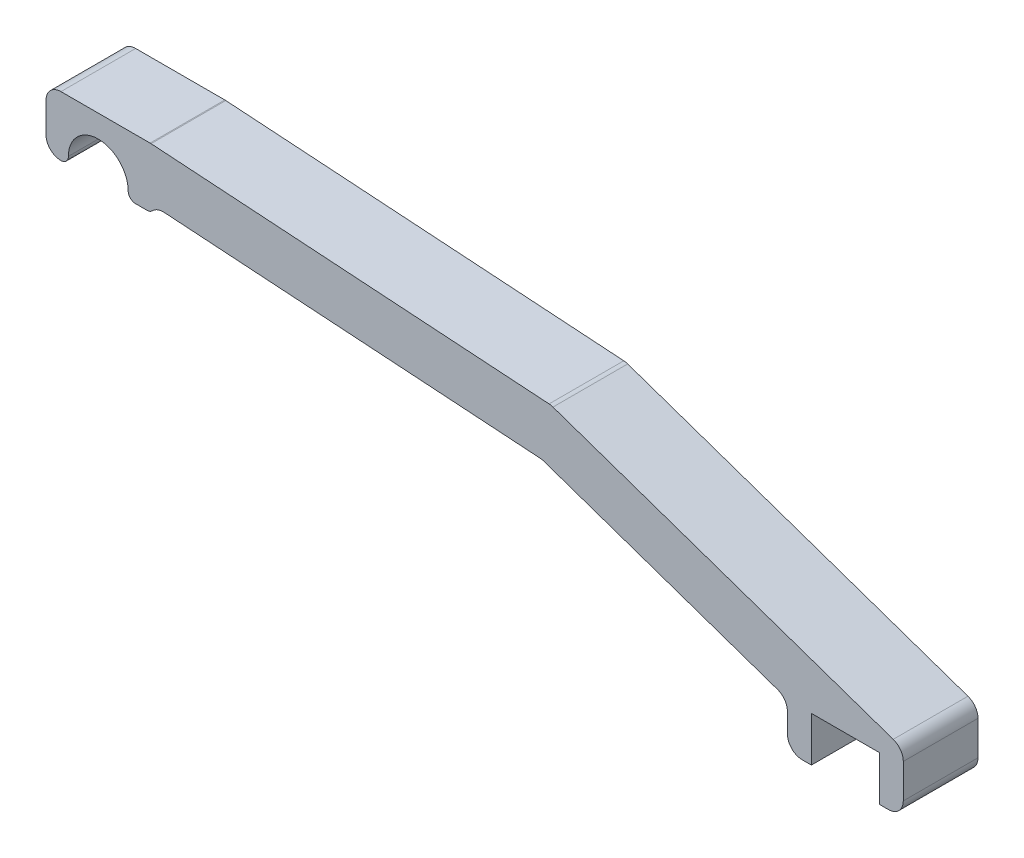
SolidWorks part; units mm, degrees
ref_plane "Спереди" through (0, 0, 0) normal (0, 0, 1) x (1, 0, 0)
ref_plane "Сверху" through (0, 0, 0) normal (0, 1, 0) x (1, 0, 0)
ref_plane "Справа" through (0, 0, 0) normal (1, 0, 0) x (0, 0, -1)
sketch "Эскиз1" plane through (0, 0, 0) normal (0, 0, 1) x (1, 0, 0)
  line L0 (95.45, -20.85) -> (95.45, -14.85)
  line L1 (92.2452, -12.85) -> (107.7548, -12.85)
  line L2 (92.2452, -12.85) -> (92.2452, -20.85)
  line L3 (92.2452, -20.85) -> (95.45, -20.85)
  line L4 (107.7548, -12.85) -> (107.7548, -20.85)
  line L5 (95.45, -14.85) -> (104.55, -14.85)
  line L6 (104.55, -14.85) -> (104.55, -20.85)
  line L7 (104.55, -20.85) -> (107.7548, -20.85)
  line L8 (0, 0) -> (60, 0) construction
  line L9 (60, 0) -> (100.8, -14.85) construction
  line L10 (60.6078, 3.4468) -> (59.3922, -3.4468)
  line L11 (-7, 7) -> (7, 7)
  line L12 (-7, 7) -> (-7, -1)
  line L14 (7, 7) -> (7, -1)
  line L15 (-7, -1) -> (-3.873, -1)
  line L16 (3.873, -1) -> (7, -1)
  line L17 (60.6078, 3.4468) -> (107.7548, -12.85)
  line L18 (59.3922, -3.4468) -> (92.2452, -14.8028)
  line L19 (60.6078, 3.4468) -> (7, 7)
  line L20 (59.3922, -3.4468) -> (7, 0.0258)
  arc A0 (3.873, -1) -> (-3.873, -1) centre (0, 0) ccw
  point P12 (100, -14.85)
  point P21 (60, 0)
  dimension "D1" = 8
  dimension "D2" = 9.1
  dimension "D3" = 6
  dimension "D4" = 2
  dimension "D5" = 14.85
  dimension "D6" = 60
  dimension "D7" = 100
  dimension "D8" = 7
  dimension "D9" = 160
  dimension "D10" = 80
  dimension "D11" = 7
  dimension "D12" = 7
  dimension "D13" = 7
  dimension "D14" = 1
extrude "Бобышка-Вытянуть1" add sketch "Эскиз1" along normal blind 10 contours A0 L16 L14 L11 L12 L15 | L20 L10 L19 L14 | L10 L18 L2 L1 L17 | L6 L7 L4 L1 L2 L3 L0 L5 region at (93.8476, -20.6755, 0) region at (79.312, -6.4147, 0) region at (33.5012, 1.7697, 0) region at (6.8388, -0.4871, 0)
fillet "Скругление1" radius 2 10 edges at (59.3922, -3.4468, 5) (7, 0.0258, 5) (-7, -1, 5) (107.7548, -12.85, 5) (7, 7, 5) (60.6078, 3.4468, 5) (-7, 7, 5) (92.2452, -14.8028, 5) (107.7548, -20.85, 5) (92.2452, -20.85, 5)
fillet "Скругление2" radius 1 3 edges at (3.873, -1, 5) (-3.873, -1, 5) (7, -1, 5)
